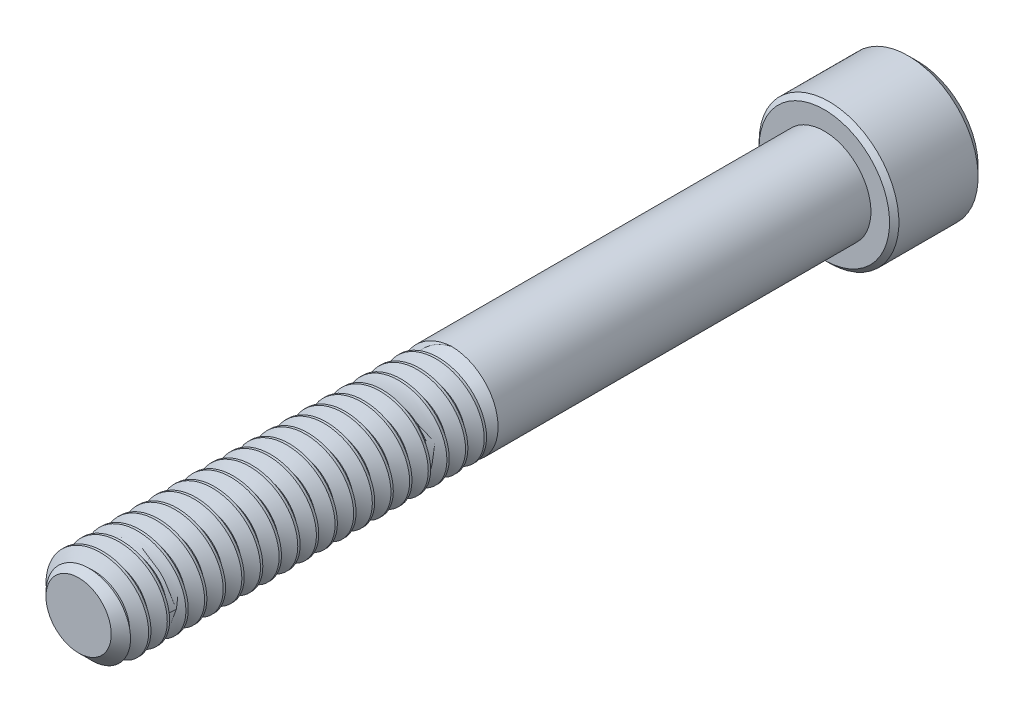
SolidWorks part; units mm, degrees
material "Cast Alloy Steel"
ref_plane "Front Plane" through (0, 0, 0) normal (0, 0, 1) x (1, 0, 0)
ref_plane "Top Plane" through (0, 0, 0) normal (0, 1, 0) x (1, 0, 0)
ref_plane "Right Plane" through (0, 0, 0) normal (1, 0, 0) x (0, 0, -1)
sketch "Sketch1" plane through (0, 0, 0) normal (0, 0, 1) x (1, 0, 0)
  line L0 (0, 3.175) -> (0, -3.175) construction
  circle A0 centre (0, 0) radius 3.175
  dimension "OD" = 6.35
extrude "Extrude1" add sketch "Sketch1" against normal blind 50.8
sketch "Sketch2" plane through (0, 0, 0) normal (0, 0, 1) x (1, 0, 0)
  circle A0 centre (0, 0) radius 3.175 construction
  circle A1 centre (0, 0) radius 3.175
curve "Helix/Spiral1" pitch 1.27 height 27.94 turns 22 parameters "pitch"=1.27
chamfer "Chamfer3" distance 0.9525 angle 45 1 edges at (3.175, 0, 0)
sketch "Sketch3" plane through (0, 0, 0) normal (1, 0, 0) x (0, 0, -1)
  line L0 (-1.1112, 3.175) -> (-0.635, 2.3501)
  line L1 (-0.635, 2.3501) -> (-0.4763, 2.3501)
  line L2 (-0.4763, 2.3501) -> (0, 3.175)
  line L3 (-1.1112, 3.175) -> (0, 3.175)
  line L4 (-0.5556, 3.175) -> (-0.5556, 2.3501) construction
  line L5 (-0.8731, 2.7626) -> (-0.2381, 2.7626) construction
  line L6 (0, 3.175) -> (0, -3.175) construction
  dimension "D1" = 0.1588
  dimension "D2" = 0.635
  dimension "D3" = 60
sweep "Cut-Sweep1" cut profiles "Sketch3" path "Helix/Spiral1"
sketch "Sketch5" plane through (0, 0, 0) normal (1, 0, 0) x (0, 0, -1)
  line L1 (50.8, 3.175) -> (25.4, 3.175)
  line L2 (50.8, 3.175) -> (50.8, 0)
  line L3 (50.8, 0) -> (25.4, 0)
  line L4 (25.4, 3.175) -> (25.4, 0) construction
  line L6 (0, 0) -> (9.9695, 0) construction
  line L8 (25.4, 3.175) -> (22.225, 0)
  line L9 (22.225, 0) -> (25.4, 0)
  line L10 (50.8, -3.175) -> (50.8, 3.175) construction
  dimension "D1" = 45
  dimension "Thread min" = 25.4
revolve "partially thread" add sketch "Sketch5" angle 360 about L6
sketch "Sketch6" plane through (0, 0, -50.8) normal (0, 0, -1) x (-1, 0, 0)
  circle A0 centre (0, 0) radius 4.7625
  dimension "head dia" = 9.525
extrude "Extrude2" add sketch "Sketch6" along normal blind 6.35
sketch "Sketch7" plane through (0, 0, -57.15) normal (0, 0, -1) x (-1, 0, 0)
  line L1 (0, 2.7496) -> (-2.3812, 1.3748)
  line L2 (-2.3812, 1.3748) -> (-2.3813, -1.3748)
  line L3 (-2.3813, -1.3748) -> (0, -2.7496)
  line L4 (0, -2.7496) -> (2.3813, -1.3748)
  line L5 (2.3813, -1.3748) -> (2.3813, 1.3748)
  line L6 (2.3813, 1.3748) -> (0, 2.7496)
  circle A0 centre (0, 0) radius 2.3813 construction
  dimension "hex dia" = 4.7625
extrude "Cut-Extrude1" cut sketch "Sketch7" against normal blind 3.5719
sketch "Sketch8" plane through (0, 0, -57.15) normal (0, 0, -1) x (-1, 0, 0)
  circle A0 centre (0, 0) radius 2.7496
extrude "Cut-Extrude2" cut sketch "Sketch8" against normal blind 0.635 draft 45
chamfer "Chamfer1" distance 0.635 angle 45 1 edges at (-4.7625, 0, -57.15)
chamfer "Chamfer2" distance 0.3175 angle 45 1 edges at (-4.7625, 0, -50.8)
sketch "Sketch9" plane through (0, 0, 0) normal (1, 0, 0) x (0, 0, -1)
  line L0 (0, 3.175) -> (0, -3.175) construction
  line L1 (6.985, 3.175) -> (6.985, -3.175) construction
  line L2 (50.8, 4.7625) -> (50.8, -4.7625) construction
  line L3 (57.15, 4.7625) -> (57.15, -4.7625) construction
  line L4 (57.15, 0) -> (0, 0) construction
  line L5 (61.6852, 3.175) -> (61.6852, -3.175) construction
  dimension "D1" = 6.985
  dimension "D2" = 6.35
  dimension "D3" = 9.525
  dimension "D4" = 50.8
  dimension "Thread Length" = 61.6852
equation "\"D3@Helix/Spiral1\" = \"Thread min@Sketch5\"+(\"pitch@Helix/Spiral1\"*2)"
equation "\"D1@Sketch3\" = \"pitch@Helix/Spiral1\"*.125"
equation "\"D2@Sketch3\" = \"pitch@Helix/Spiral1\"*.5"
equation "\"D1@Cut-Extrude1\" = \"hex dia@Sketch7\"*.75"
equation "\"D1@Chamfer1\" = \"head depth@Extrude2\"/10"
equation "\"D1@Sketch9\" = \"pitch@Helix/Spiral1\"*5.5"
equation "\"D1@Chamfer2\" = \"D1@Chamfer1\"/2"
equation "\"D1@Cut-Extrude2\" = \"D1@Chamfer2\"*2"
equation "\"D1@Chamfer3\" = \"pitch@Helix/Spiral1\"*.750"
equation "\"D2@Sketch9\" = \"head depth@Extrude2\""
equation "\"D3@Sketch9\" = \"head dia@Sketch6\""
equation "\"D4@Sketch9\" = \"screw length@Extrude1\""
